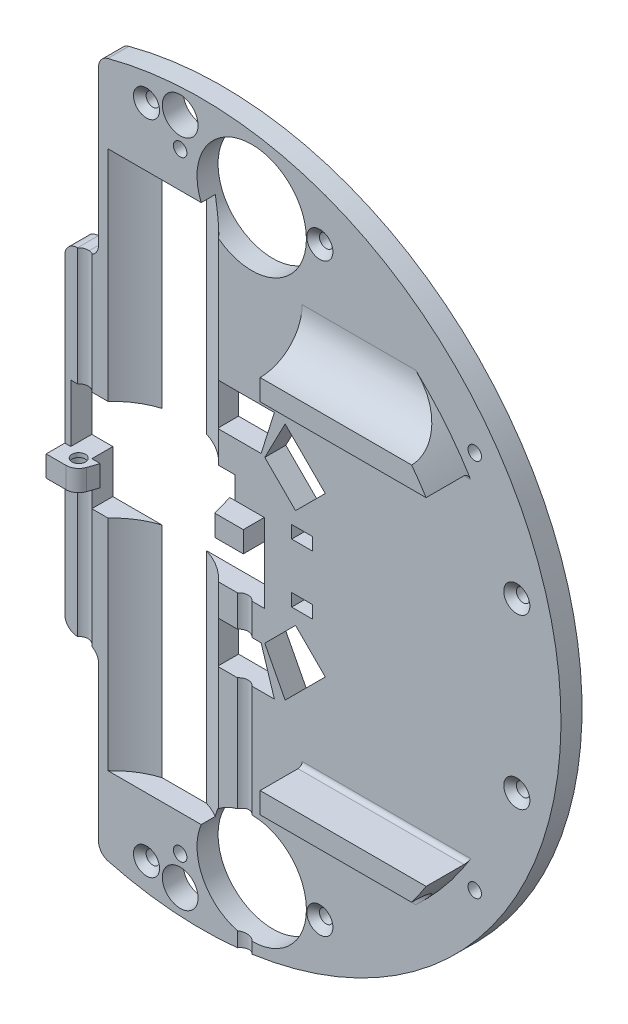
SolidWorks part; units mm, degrees
material "PVC 0.007 Plasticized"
ref_plane "Front Plane" through (0, 0, 0) normal (1, 0, 0) x (0, 1, 0)
ref_plane "Top Plane" through (0, 0, 0) normal (0, 0, 1) x (0, 1, 0)
ref_plane "Right Plane" through (0, 0, 0) normal (0, 1, 0) x (-1, 0, 0)
sketch "Sketch1" plane through (0, 0, 0) normal (0, 0, 1) x (0, 1, 0)
  line L0 (0, 0) -> (0, -81.5088) construction
  line L1 (-40, 24.3888) -> (-40, 32.4114)
  line L2 (-40, 32.4114) -> (40, 32.4114)
  line L6 (-81.9478, 24.3888) -> (-40, 24.3888)
  line L7 (81.941, 24.4114) -> (40, 24.4114)
  line L8 (40, 24.4114) -> (40, 32.4114)
  arc A0 (-81.9478, 24.3888) -> (81.941, 24.4114) centre (0, 0) ccw
  circle A1 centre (-20, -75) radius 1.6
  circle A2 centre (20, -75) radius 1.6
  circle A3 centre (-69.5, -28.2) radius 1.6
  circle A9 centre (-78, 13) radius 1.6
  circle A10 centre (-79.5, 5) radius 4.25
  circle A11 centre (-69, -12) radius 13
  circle A16 centre (69, -12) radius 13
  circle A17 centre (79.5, 5) radius 4.25
  circle A18 centre (78, 13) radius 1.6
  circle A19 centre (69.5, -28.2) radius 1.6
  dimension "D1" = 171
  dimension "D3" = 3.2
  dimension "D7" = 3.2
  dimension "D8" = 78
  dimension "D13" = 5
  dimension "D14" = 69
  dimension "D16" = 40
  dimension "D2" = 75
  dimension "D4" = 20
  dimension "D5" = 69.5
  dimension "D6" = 28.2
  dimension "D9" = 40
  dimension "D10" = 13
  dimension "D11" = 8
  dimension "D12" = 79.5
  dimension "D15" = 12
extrude "Boss-Extrude2" add sketch "Sketch1" along normal blind 5
sketch "Sketch2" plane through (0, 0, 5) normal (0, 0, 1) x (1, 0, 0)
  line L1 (60, 45) -> (24, 45)
  line L3 (63.4429, 40) -> (24, 40)
  line L4 (24, 45) -> (24, 40)
  line L6 (24, -45) -> (24, -40)
  line L7 (63.4429, -40) -> (24, -40)
  line L8 (60, -45) -> (24, -45)
  arc A3 (60, -45) -> (63.4429, -40) centre (0, 0) ccw
  arc A4 (63.4429, 40) -> (60, 45) centre (0, 0) ccw
  dimension "D1" = 150
  dimension "D2" = 40
extrude "Boss-Extrude3" add sketch "Sketch2" along normal blind 10
fillet "Fillet1" radius 10 2 edges at (42, -45, 5) (42, 45, 5)
fillet "Fillet2" radius 1 2 edges at (43.7214, -40, 5) (43.7214, 40, 5)
sketch "Sketch5" plane through (0, 0, 5) normal (0, 0, 1) x (1, 0, 0)
  line L0 (0, 0) -> (93.3614, 0) construction
  circle A0 centre (65, 45) radius 1.6
  circle A2 centre (-5, 72.5) radius 1.6
  circle A4 centre (65, -45) radius 1.6
  circle A5 centre (-5, -72.5) radius 1.6
  dimension "D1" = 3.2
  dimension "D5" = 3.2
  dimension "D2" = 65
  dimension "D3" = 45
  dimension "D4" = 5
  dimension "D6" = 72.5
extrude "Cut-Extrude2" cut sketch "Sketch5" against normal blind 10
chamfer "Chamfer1" distance 1.5 angle 45 6 edges at (-14.6, -78, 5) (29.8, -69.5, 5) (76.6, -20, 5) (73.4, 20, 5) (26.6, 69.5, 5) (-11.4, 78, 5)
chamfer "Chamfer2" distance 1.5 angle 45 4 edges at (-3.4, 72.5, 0) (-3.4, -72.5, 0) (66.6, -45, 0) (66.6, 45, 0)
sketch "Sketch9" plane through (0, 0, 5) normal (0, 0, 1) x (1, 0, 0)
  line L1 (17.112, -24.1831) -> (24.1831, -17.112) construction
  line L6 (14.2376, -19.4864) -> (3.8798, -19.4864)
  line L8 (15.1085, -19.1155) -> (22.4153, -11.8087)
  line L10 (22.4153, -11.8087) -> (29.4864, -18.8798)
  line L11 (19.9404, -28.4257) -> (29.4864, -18.8798)
  line L12 (11.8087, -22.4153) -> (29.4864, -18.8798) construction
  line L13 (22.4153, -11.8087) -> (18.8798, -29.4864) construction
  line L14 (0, 0) -> (90.6538, 0) construction
  line L23 (17.3798, -29.4864) -> (3.8798, -29.4864)
  line L24 (3.8798, -19.4864) -> (3.8798, -29.4864)
  line L25 (18.8798, -19.4864) -> (3.8798, -29.4864) construction
  line L26 (18.8798, -29.4864) -> (3.8798, -19.4864) construction
  line L32 (15.1085, -19.1155) -> (19.9404, -28.4257)
  line L33 (17.3798, -29.4864) -> (14.2376, -19.4864)
  line L34 (17.3798, 29.4864) -> (14.2376, 19.4864)
  line L35 (14.2376, 19.4864) -> (3.8798, 19.4864)
  line L36 (3.8798, 19.4864) -> (3.8798, 29.4864)
  line L37 (17.3798, 29.4864) -> (3.8798, 29.4864)
  line L38 (15.1085, 19.1155) -> (19.9404, 28.4257)
  line L39 (15.1085, 19.1155) -> (22.4153, 11.8087)
  line L40 (22.4153, 11.8087) -> (29.4864, 18.8798)
  line L41 (19.9404, 28.4257) -> (29.4864, 18.8798)
  point P1 (11.3798, -24.4864)
  point P6 (20.6475, -20.6475)
  dimension "D1" = 10
  dimension "D2" = 15
  dimension "D3" = 15
  dimension "D4" = 10
  dimension "D6" = 1.5
  dimension "D7" = 1.5
extrude "Cut-Extrude3" cut sketch "Sketch9" against normal blind 10
sketch "Sketch10" plane through (0, 0, 0) normal (0, 1, 0) x (-1, 0, 0)
  line L0 (-85.5, 0) -> (24.4114, 0) construction
  circle A0 centre (9, 17) radius 17.8
  dimension "D1" = 35.6
  dimension "D2" = 17
  dimension "D3" = 9
extrude "Cut-Extrude4" cut sketch "Sketch10" against normal blind 64 and the other way blind 64
sketch "Sketch11" plane through (0, 0, 5) normal (0, 0, 1) x (1, 0, 0)
  line L0 (-26, -1.7) -> (-31, -1.7)
  line L1 (8, 12) -> (-25, 12)
  line L3 (15, -12) -> (-26, -12)
  line L4 (-26, -1.7) -> (-26, -12)
  line L5 (15, -12) -> (15, 1.7)
  line L6 (8, 12) -> (8, 1.7)
  line L7 (8, 1.7) -> (15, 1.7)
  line L8 (-31, -1.7) -> (-31, 12)
  line L9 (-31, 12) -> (-25, 12)
  point P0 (0, 0)
  dimension "D1" = 24
  dimension "D2" = 12
  dimension "D3" = 6
  dimension "D4" = 15
  dimension "D5" = 7
  dimension "D6" = 1.7
  dimension "D7" = 1.7
  dimension "D8" = 5
extrude "Cut-Extrude5" cut sketch "Sketch11" against normal blind 62.5
sketch "Sketch12" plane through (0, 0, 5) normal (0, 0, 1) x (1, 0, 0)
  line L1 (10.2402, 0) -> (10.2402, 1.7) construction
  line L2 (-6.5732, 0.8) -> (-6.5732, 1.7) construction
  line L3 (-6.5732, 1.7) -> (10.2402, 1.7) construction
  line L4 (-16.3028, 0) -> (-16.3028, -1.7) construction
  line L5 (-8.6264, 0) -> (-8.6264, -0.9) construction
  dimension "D1" = 1.7
  dimension "D2" = 1.7
ref_plane "Plane2" through (0, 1.7, 0) normal (0, -1, 0) x (1, 0, 0)
sketch "Sketch13" plane through (0, 0, 5) normal (0, 0, 1) x (1, 0, 0)
  line L1 (15, 1.7) -> (6.7929, 1.7)
  line L2 (15, 1.7) -> (15, 6.7)
  line L3 (15, 6.7) -> (6.7929, 6.7)
  line L4 (6.7929, 1.7) -> (6.7929, 6.7)
  dimension "D1" = 5
extrude "Boss-Extrude4" add sketch "Sketch13" along normal blind 5
sketch "Sketch14" plane through (0, 1.7, 0) normal (0, -1, 0) x (1, 0, 0)
  circle A1 centre (10.3299, 6.4392) radius 2.25
  dimension "D2" = 4.5
extrude "Cut-Extrude6" cut sketch "Sketch14" against normal blind 4 and the other way blind 110
sketch "Sketch15" plane through (0, 1.7, 0) normal (0, -1, 0) x (1, 0, 0)
  line L2 (6.7929, 5) -> (6.7929, 10)
  line L3 (6.7929, 10) -> (8.2341, 10)
  line L4 (6.7929, 5) -> (8.2341, 10)
extrude "Cut-Extrude7" cut sketch "Sketch15" against normal blind 15
sketch "Sketch16" plane through (0, 0, 5) normal (0, 0, 1) x (1, 0, 0)
  line L0 (-32.4114, 40) -> (-32.4114, -40) construction
  line L1 (-32.4114, -1.7) -> (-24, -1.7)
  line L2 (-32.4114, -1.7) -> (-32.4114, -6.7)
  line L3 (-32.4114, -6.7) -> (-24, -6.7)
  line L4 (-24, -1.7) -> (-24, -6.7)
  dimension "D1" = 5
  dimension "D2" = 1.7
extrude "Boss-Extrude5" add sketch "Sketch16" along normal blind 5
sketch "Sketch17" plane through (0, -6.7, 0) normal (0, -1, 0) x (1, 0, 0)
  circle A0 centre (-27.6683, 6.4392) radius 2.25
  dimension "D1" = 4.5
extrude "Cut-Extrude8" cut sketch "Sketch17" against normal blind 4 and the other way blind 40
sketch "Sketch18" plane through (0, -6.7, 0) normal (0, -1, 0) x (1, 0, 0)
  line L0 (-24, 5) -> (-24.8314, 7.4156)
  line L1 (-32.4114, 10) -> (-24, 10) construction
  line L2 (-25.7209, 10) -> (-24, 10)
  line L3 (-24, 10) -> (-24, 5)
  line L5 (-27.6683, 9.4394) -> (-32.4114, 9.4394)
  line L6 (-32.4114, 10) -> (-32.4114, 5) construction
  line L7 (-32.4114, 9.4394) -> (-32.4114, 10)
  line L8 (-32.4114, 10) -> (-25.7209, 10)
  arc A1 (-24.8314, 7.4156) -> (-27.6683, 9.4394) centre (-27.6683, 6.4392) ccw
extrude "Cut-Extrude9" cut sketch "Sketch18" against normal blind 7
sketch "Sketch19" plane through (0, -2.7, 0) normal (0, -1, 0) x (1, 0, 0)
  circle A0 centre (-27.6683, 6.4392) radius 1.6
  dimension "D1" = 3.2
extrude "Cut-Extrude10" cut sketch "Sketch19" against normal blind 7
sketch "Sketch20" plane through (0, -1.7, 0) normal (0, 1, 0) x (-1, 0, 0)
  circle A0 centre (27.6683, 6.4392) radius 2.25
  dimension "D1" = 4.5
extrude "Cut-Extrude11" cut sketch "Sketch20" along normal blind 45
sketch "Sketch21" plane through (0, 0, 0) normal (0, 0, -1) x (1, 0, 0)
  line L1 (69.738, 4) -> (6.369, 4)
  line L2 (69.738, 4) -> (69.738, -4)
  line L3 (69.738, -4) -> (6.369, -4)
  line L4 (6.369, 4) -> (6.369, -4)
  dimension "D1" = 8
  dimension "D2" = 4
extrude "Cut-Extrude12" cut sketch "Sketch21" against normal blind 3
sketch "Sketch22" plane through (0, 0, 0) normal (0, 0, -1) x (1, 0, 0)
  line L0 (0, 0) -> (46.1564, 0) construction
  line L1 (21.5, -5.5) -> (26.5, -5.5)
  line L2 (21.5, -5.5) -> (21.5, -8.5)
  line L3 (21.5, -8.5) -> (26.5, -8.5)
  line L4 (26.5, -5.5) -> (26.5, -8.5)
  line L5 (21.5, -5.5) -> (26.5, -8.5) construction
  line L6 (21.5, -8.5) -> (26.5, -5.5) construction
  line L11 (21.5, 8.5) -> (26.5, 5.5) construction
  line L12 (21.5, 5.5) -> (26.5, 8.5) construction
  line L13 (26.5, 5.5) -> (26.5, 8.5)
  line L14 (21.5, 8.5) -> (26.5, 8.5)
  line L15 (21.5, 5.5) -> (21.5, 8.5)
  line L16 (21.5, 5.5) -> (26.5, 5.5)
  point P0 (24, -7)
  point P12 (24, 7)
  dimension "D1" = 5
  dimension "D2" = 3
  dimension "D3" = 7
  dimension "D4" = 24
extrude "Cut-Extrude13" cut sketch "Sketch22" against normal blind 5
sketch "Sketch23" plane through (0, 0, 5) normal (0, 0, 1) x (1, 0, 0)
fillet "Fillet3" radius 3 6 edges at (-24.3888, -40, 2.5) (-32.4114, -40, 2.5) (-24.4114, 40, 2.5) (-32.4114, 40, 2.5) (-24.4114, 81.941, 2.5) (-24.3888, -81.9478, 2.5)
